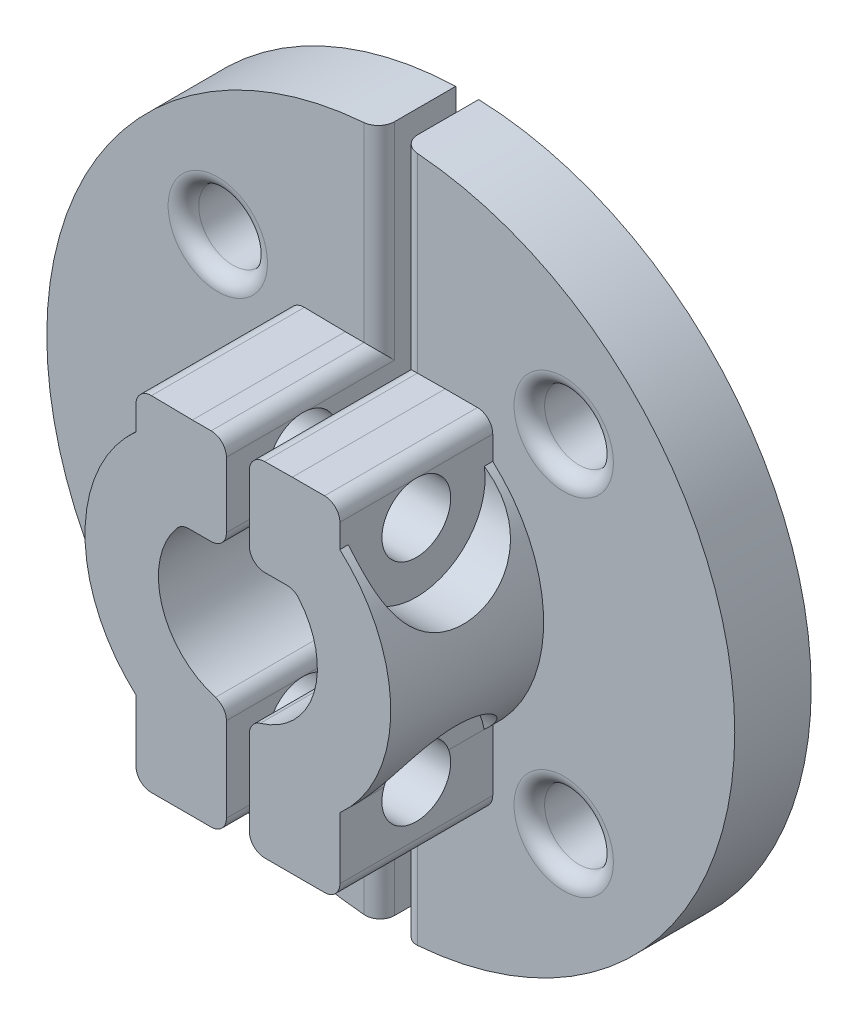
SolidWorks part; units mm, degrees
ref_plane "Front Plane" through (0, 0, 0) normal (0, 0, 1) x (1, 0, 0)
ref_plane "Top Plane" through (0, 0, 0) normal (0, 1, 0) x (1, 0, 0)
ref_plane "Right Plane" through (0, 0, 0) normal (1, 0, 0) x (0, 0, -1)
sketch "Sketch1" plane through (0, 0, 0) normal (0, 0, 1) x (1, 0, 0)
  line L0 (0, 0) -> (0, 22.5) construction
  line L1 (0, 0) -> (22.5, 0) construction
  line L2 (15.9099, 15.9099) -> (0, 0) construction
  circle A7 centre (0, 0) radius 22.5
  circle A8 centre (0, 0) radius 5.2
  circle A10 centre (11.3137, 11.3137) radius 2.25
  circle A11 centre (-11.3137, 11.3137) radius 2.25
  circle A12 centre (11.3137, -11.3137) radius 2.25
  circle A13 centre (-11.3137, -11.3137) radius 2.25
  point P2 (9.7227, 9.7227)
  point P4 (-13.005, 12.7976)
  point P7 (-15.9099, 15.9099)
  point P11 (15.9099, 15.9099)
  point P15 (7.955, 7.955)
  dimension "D1" = 45
  dimension "D2" = 10.4
  dimension "D3" = 16
  dimension "D7" = 2.5
  dimension "D5" = 4.5
  dimension "D4" = 45
extrude "Boss-Extrude1" add sketch "Sketch1" along normal blind 15
sketch "Sketch2" plane through (0, 0, 15) normal (0, 0, 1) x (1, 0, 0)
  circle A0 centre (0, 0) radius 10
  circle A2 centre (11.3137, 11.3137) radius 2.25 construction
  point P13 (9.1702, 10.6296)
  point P14 (9.7238, 9.7217)
  point P15 (7.1244, 7.0174)
extrude "Cut-Extrude1" cut sketch "Sketch2" against normal blind 10 flip side to cut
sketch "Sketch4" plane through (0, 0, 5) normal (0, 0, 1) x (1, 0, 0)
  line L1 (0.75, -24.0665) -> (-0.75, -24.0665)
  line L2 (0.75, -24.0665) -> (0.75, 24.0665)
  line L3 (0.75, 24.0665) -> (-0.75, 24.0665)
  line L4 (-0.75, -24.0665) -> (-0.75, 24.0665)
  line L5 (0.75, -24.0665) -> (-0.75, 24.0665) construction
  line L6 (0.75, 24.0665) -> (-0.75, -24.0665) construction
  point P0 (0, 0)
  dimension "D1" = 1.5
extrude "Cut-Extrude2" cut sketch "Sketch4" against normal through all both and the other way through all
sketch "Sketch5" plane through (0, 0, 5) normal (0, 0, 1) x (1, 0, 0)
  line L2 (5.75, 8.1815) -> (5.75, 9.9718)
  line L6 (2.3898, 9.9718) -> (2.3306, 9.7246) construction
  line L11 (0.75, 9.9718) -> (5.75, 9.9718)
  line L19 (-0.75, 9.9718) -> (-5.75, 9.9718)
  line L20 (-5.75, 8.1815) -> (-5.75, 9.9718)
  arc A8 (5.75, 8.1815) -> (0.75, 9.9718) centre (0, 0) ccw
  arc A9 (-0.75, 9.9718) -> (-5.75, 8.1815) centre (0, 0) ccw
  point P0 (0, 0)
  point P10 (0, 4.975)
sketch "Sketch9" plane through (0, 0, 0) normal (0, 0, -1) x (-1, 0, 0)
  line L0 (-3.6538, 3.7) -> (-0.75, 3.7)
  line L1 (-0.75, 5.1456) -> (-0.75, 3.7)
  line L2 (0.75, 5.1456) -> (0.75, 3.7)
  line L3 (0.75, 3.7) -> (3.6538, 3.7)
  arc A0 (-0.75, 5.1456) -> (0.75, 5.1456) centre (0, 0) ccw
  point P3 (0, 5.2)
  arc M6 (0.75, 5.1456) -> (0.75, -5.1456) centre (0, 0) cw
  dimension "D1" = 1.5
extrude "Boss-Extrude7" add sketch "Sketch9" against normal blind 15 contours L1 A0 L0 | L2 L3 M6
sketch "Sketch16" plane through (0, 0, 5) normal (0, 0, 1) x (1, 0, 0)
  line L1 (-2.9749, 9.9718) -> (-0.75, 9.9718)
  line L3 (3.5602, 10) -> (0.75, 9.9718)
  line L8 (6.6702, 3.475) -> (6.6702, 10)
  line L9 (-6.6702, 3.475) -> (-6.6702, 10.0271)
  line L10 (-6.6702, 10.0271) -> (-2.9749, 9.9718)
  line L13 (3.5602, 10) -> (6.6702, 10)
  line L14 (-6.6702, 3.475) -> (-0.75, 9.9718)
  line L15 (0.75, 9.9718) -> (6.6702, 3.475)
  line L16 (0, 0) -> (25.9238, 0) construction
  line L25 (0, 0) -> (0, -12.1547) construction
  line L26 (-0.75, -5.4759) -> (-6.67, -5.4759)
  line L27 (-0.75, -5.4759) -> (-0.75, -12.4759)
  line L28 (-0.75, -12.4759) -> (-6.67, -12.4759)
  line L29 (-6.67, -5.4759) -> (-6.67, -12.4759)
  line L30 (0.75, -12.4759) -> (6.67, -12.4759)
  line L31 (6.67, -5.4759) -> (6.67, -12.4759)
  line L32 (0.75, -5.4759) -> (6.67, -5.4759)
  line L33 (0.75, -5.4759) -> (0.75, -12.4759)
  line L34 (-6.67, -5.4759) -> (-0.75, -9.9718)
  line L35 (6.67, -5.4759) -> (0.75, -9.9718)
  circle A0 centre (11.3137, 11.3137) radius 2.25 construction
  circle A1 centre (-11.3137, 11.3137) radius 2.25 construction
  arc A2 (0.75, -9.9718) -> (0.75, 9.9718) centre (0, 0) ccw construction
  point P0 (9.1702, 10.6296)
  point P20 (-9.1702, 10.6296)
  dimension "D2" = 2.5
  dimension "D1" = 2.5
  dimension "D3" = 5.92
extrude "Boss-Extrude9" add sketch "Sketch16" along normal blind 10 contours L9 L10 L1 L14 | L8 L13 L3 L15 | L31 L30 L33 L32 | L29 L28 L27 L26
fillet "Fillet1" radius 1 1 edges at (-3.6538, 3.7, 7.5)
fillet "Fillet2" radius 1 1 edges at (3.6538, 3.7, 7.5)
fillet "Fillet3" radius 1 1 edges at (-6.6702, 10.0271, 10)
fillet "Fillet4" radius 1 1 edges at (6.6702, 10, 10)
sketch "Sketch25" plane through (0.75, 0, 0) normal (-1, 0, 0) x (0, 0, 1)
  line L0 (15, 3.7) -> (15, 10.0121) construction
  line L1 (5, 3.7) -> (20.5726, 3.7) construction
  line L2 (0, 0) -> (18.612, 0) construction
  line L3 (5, 10.0121) -> (5, 3.7) construction
  line L4 (5, -7.4506) -> (5, 7.4504) construction
  line L5 (10, 6.7566) -> (10, -11.3851) construction
  line L6 (10, 6.7566) -> (10, 12.9642) construction
  line L7 (15, 10.0121) -> (5, 10.0121) construction
  line L8 (15, -12.4759) -> (5, -12.4759) construction
  line L9 (14.3175, -5.1456) -> (26.7376, -5.1456) construction
  line L10 (15, -5.1456) -> (0, -5.1456) construction
  line L11 (14.3175, -5.1456) -> (-3.6957, -5.1456) construction
  circle A0 centre (10, 6.7566) radius 2.25
  circle A2 centre (10, -8.2056) radius 2.25
  point P18 (10, 10.0121)
  point P21 (10, 9.0066)
  point P24 (10, -10.4556)
  point P25 (10, -12.4759)
  point P31 (10, -5.9556)
  point P33 (10, 4.5066)
  dimension "D1" = 0.8066
  dimension "D3" = 4.5
  dimension "D5" = 4.5
  dimension "D2" = 0.81
extrude "Cut-Extrude3" cut sketch "Sketch25" against normal through all both and the other way through all
fillet "Fillet10" radius 1 1 edges at (-6.67, -12.4759, 10)
fillet "Fillet11" radius 1 1 edges at (6.67, -12.4759, 10)
sketch "Sketch26" plane through (-6.6702, 0, 0) normal (-1, 0, 0) x (0, 0, 1)
  circle A0 centre (10, 6.7566) radius 4.5
  circle A1 centre (10, -8.2056) radius 4.5
  dimension "D1" = 9
  dimension "D2" = 9
extrude "Cut-Extrude4" cut sketch "Sketch26" along normal through all
sketch "Sketch27" plane through (6.6702, 0, 0) normal (1, 0, 0) x (0, 0, -1)
  circle A0 centre (-10, 6.7566) radius 4.5
  circle A1 centre (-10, -8.2056) radius 4.5
  dimension "D1" = 9
  dimension "D2" = 9
extrude "Cut-Extrude5" cut sketch "Sketch27" along normal through all
fillet "Fillet14" radius 1 1 edges at (-0.75, -5.1456, 7.5)
fillet "Fillet15" radius 1 1 edges at (-0.75, 9.9718, 10)
fillet "Fillet16" radius 1 1 edges at (0.75, 9.9718, 10)
fillet "Fillet17" radius 1 1 edges at (-0.75, 15.7297, 5)
fillet "Fillet18" radius 1 1 edges at (0.75, 15.7347, 5)
fillet "Fillet19" radius 1 1 edges at (-0.75, -12.4759, 10)
fillet "Fillet20" radius 1 1 edges at (0.75, -12.4759, 10)
fillet "Fillet21" radius 1 2 edges at (-1.0429, -12.183, 5) (-0.75, -16.9817, 5)
fillet "Fillet22" radius 1 1 edges at (0.75, -16.9817, 5)
fillet "Fillet25" radius 1 2 edges at (-9.0637, 11.3137, 5) (-13.5637, 11.3137, 0)
fillet "Fillet26" radius 1 2 edges at (13.5637, 11.3137, 5) (13.5637, 11.3137, 0)
fillet "Fillet27" radius 1 2 edges at (13.5637, -11.3137, 5) (9.0637, -11.3137, 0)
fillet "Fillet33" radius 1 2 edges at (-9.0637, -11.3137, 5) (-9.0637, -11.3137, 0)
fillet "Fillet35" radius 1 1 edges at (0.75, -5.1456, 7.5)
fillet "Fillet36" radius 1 1 edges at (-0.75, 3.7, 7.5)
fillet "Fillet37" radius 1 1 edges at (0.75, 3.7, 7.5)
